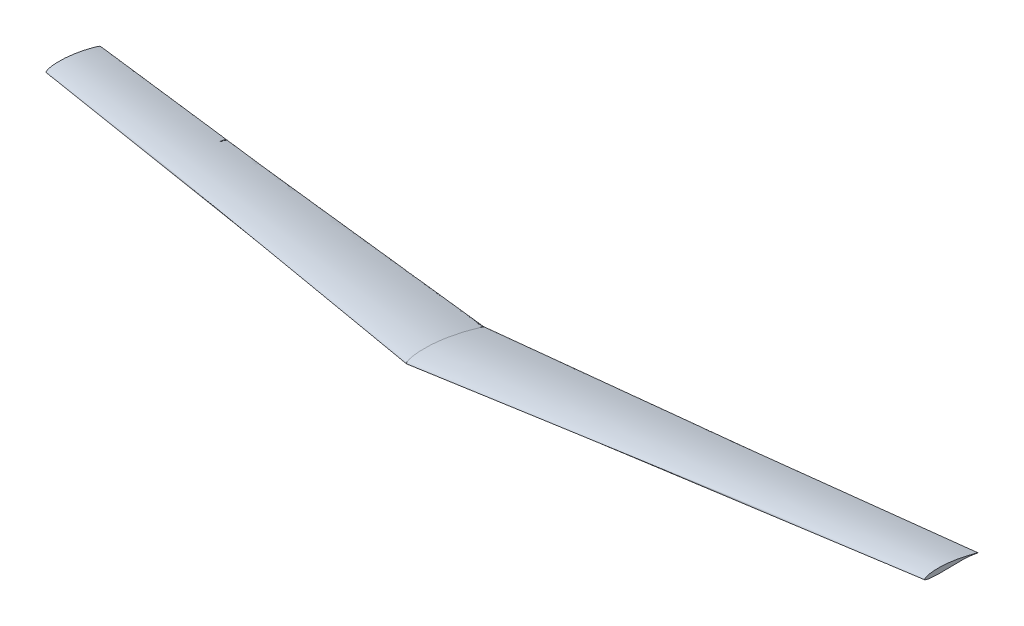
SolidWorks part; units mm, degrees
ref_plane "Front Plane" through (0, 0, 0) normal (0, 0, 1) x (1, 0, 0)
ref_plane "Top Plane" through (0, 0, 0) normal (0, 1, 0) x (1, 0, 0)
ref_plane "Right Plane" through (0, 0, 0) normal (1, 0, 0) x (0, 0, -1)
curve "Curve1" [suppressed]
  spline degree 3 poles (990.8864, 1.4626, 0) (1002.2961, -0.4112, 0) (990.8441, 1.8134, 0) (981.5017, 3.7617, 0) (958.72, 8.2838, 0) (930.7788, 13.882, 0) (894.3584, 21.0524, 0) (851.6093, 29.1958, 0) (802.7012, 37.9605, 0) (748.6568, 46.8178, 0) (690.3336, 55.2598, 0) (628.7485, 62.8578, 0) (564.9593, 69.3102, 0) (500.0529, 74.2901, 0) (435.1446, 77.6383, 0) (381.5431, 78.8952, 0) (339.5074, 78.8514, 0) (308.9256, 78.291, 0) (279.1596, 77.1918, 0) (250.3368, 75.5511, 0) (222.5834, 73.3929, 0) (196.0179, 70.7426, 0) (170.7576, 67.5923, 0) (146.9006, 64.0143, 0) (124.5538, 60.0239, 0) (103.8161, 55.6758, 0) (84.7697, 51.0327, 0) (67.4899, 46.1315, 0) (52.0474, 40.9763, 0) (38.4901, 35.5666, 0) (26.9107, 29.8179, 0) (17.3482, 23.8003, 0) (9.8808, 17.6898, 0) (4.4583, 11.8176, 0) (1.0945, 6.5163, 0) (-0.4235, 1.7367, 0) (0.8173, -2.5835, 0) (4.659, -5.507, 0) (10.1684, -7.8354, 0) (17.6608, -10.1699, 0) (27.1608, -12.5656, 0) (38.6719, -15.0199, 0) (52.1627, -17.3731, 0) (67.5741, -19.4941, 0) (84.8387, -21.2782, 0) (103.8748, -22.7648, 0) (124.6076, -23.8975, 0) (146.9475, -24.7252, 0) (170.7979, -25.1679, 0) (196.0544, -25.2499, 0) (222.6146, -24.8933, 0) (250.3648, -24.0804, 0) (279.1846, -22.7848, 0) (308.9466, -21.0099, 0) (339.5213, -18.768, 0) (381.5575, -15.3047, 0) (435.122, -10.2918, 0) (499.9862, -3.9917, 0) (564.857, 2.0129, 0) (628.629, 7.1599, 0) (690.2143, 10.984, 0) (748.5563, 13.2668, 0) (802.6371, 13.9274, 0) (851.5834, 13.0931, 0) (894.3694, 11.1362, 0) (930.8016, 8.4, 0) (958.7658, 5.6402, 0) (981.4948, 2.6953, 0) (990.8864, 1.4626, 0) (1002.2961, -0.4112, 0) (990.8441, 1.8134, 0) knots -0.01889 -0.00847 -0.00213 0 0.002148 0.00855 0.019093 0.033602 0.051812 0.073403 0.097969 0.12507 0.15422 0.18491 0.21662 0.248811 0.280949 0.312507 0.327907 0.342969 0.357635 0.371852 0.385562 0.398705 0.41124 0.423118 0.434295 0.444729 0.454376 0.463215 0.471223 0.478387 0.484735 0.490273 0.49502 0.498937 0.502002 0.504262 0.5061 0.508218 0.511109 0.514949 0.519768 0.525568 0.532309 0.53997 0.548516 0.557914 0.568141 0.57915 0.590897 0.603335 0.616414 0.630088 0.644296 0.658978 0.674077 0.689528 0.721211 0.753454 0.785684 0.817334 0.84785 0.876721 0.903468 0.927655 0.94889 0.966808 0.98111 0.99153 0.99787 1 1.002148 1.00855 1.019093 periodic
sketch "Sketch1" plane through (0, 0, 0) normal (1, 0, 0) x (0, 0, -1)
  line L0 (1494.292, -130.7336) -> (0, 0) construction
  line L1 (0, 0) -> (5.8072, 66.3764) construction
  line L2 (0, 0) -> (1494.292, 0) construction
  spline S3 degree 3 poles (1480.8596, -127.3779) (1497.6707, -131.6429) (1480.8414, -126.8482) (1467.1294, -122.7373) (1433.6627, -113.0547) (1392.6234, -101.1016) (1339.1137, -85.7106) (1276.2708, -68.053) (1204.3031, -48.6762) (1124.671, -28.5018) (1038.5911, -8.3988) (947.5278, 10.8615) (853.0235, 28.6927) (756.6606, 44.4666) (660.0853, 57.8023) (580.1395, 66.5612) (517.3119, 71.8914) (471.5356, 74.9795) (426.9096, 77.1576) (383.6234, 78.4053) (341.8692, 78.7424) (301.8269, 78.1915) (263.6712, 76.7259) (227.5579, 74.4409) (193.6485, 71.3458) (162.098, 67.5095) (133.0373, 63.0152) (106.5835, 57.9085) (82.8432, 52.1864) (61.8875, 45.8418) (43.8442, 38.7368) (28.7808, 30.9709) (16.8364, 22.7974) (7.9787, 14.7174) (2.271, 7.2265) (-0.6112, 0.2784) (0.6887, -6.3375) (6.0548, -11.1998) (13.9897, -15.3868) (24.8874, -19.8374) (38.7775, -24.6371) (55.6657, -29.7827) (75.5256, -35.0313) (98.2856, -40.1793) (123.8584, -45.0617) (152.117, -49.727) (182.9566, -54.0811) (216.2372, -58.1856) (251.8246, -61.9088) (289.5597, -65.2734) (329.2996, -68.1497) (370.8764, -70.497) (414.1136, -72.26) (458.8206, -73.4277) (504.802, -74.0019) (568.0694, -74.2218) (648.7647, -73.6057) (746.5125, -72.5163) (844.2323, -71.8695) (940.1997, -72.3633) (1032.7294, -74.5533) (1120.2142, -78.6306) (1201.1222, -84.5852) (1274.1651, -92.1149) (1337.8573, -100.5317) (1391.9537, -109.2974) (1433.3918, -117.0115) (1466.9821, -124.3302) (1480.8596, -127.3779) (1497.6707, -131.6429) (1480.8414, -126.8482) knots -0.01889 -0.00847 -0.00213 0 0.002148 0.00855 0.019093 0.033602 0.051812 0.073403 0.097969 0.12507 0.15422 0.18491 0.21662 0.248811 0.280949 0.312507 0.327907 0.342969 0.357635 0.371852 0.385562 0.398705 0.41124 0.423118 0.434295 0.444729 0.454376 0.463215 0.471223 0.478387 0.484735 0.490273 0.49502 0.498937 0.502002 0.504262 0.5061 0.508218 0.511109 0.514949 0.519768 0.525568 0.532309 0.53997 0.548516 0.557914 0.568141 0.57915 0.590897 0.603335 0.616414 0.630088 0.644296 0.658978 0.674077 0.689528 0.721211 0.753454 0.785684 0.817334 0.84785 0.876721 0.903468 0.927655 0.94889 0.966808 0.98111 0.99153 0.99787 1 1.002148 1.00855 1.019093 only from (1494.292, -130.7336) to (1494.292, -130.7336)
  dimension "D1" = 1500
  dimension "D2" = 5
ref_plane "Plane1" through (0, 0, 0) normal (0, 0.9962, -0.0872) x (1, -0.0003, -0.0038)
sketch "Sketch2" plane through (0, 0, 0) normal (0, 0.9962, -0.0872) x (1, -0.0003, -0.0038)
  line L0 (8500, 0) -> (0, 0) construction
  line L2 (8500, 0) -> (8500, 1498.7793) construction
  line L3 (5.7188, 1499.9891) -> (0, 0) construction
  line L4 (8500, 1498.7793) -> (8500, 2538.7793)
  line L5 (8500, 2538.7793) -> (5.7188, 1499.9891)
  line L6 (5.7188, 1499.9891) -> (0, 0)
  line L8 (0, 0) -> (8500, 1498.7793)
  point P0 (0, 0)
  point P9 (10000, 1763.2698)
  point P10 (0, 0)
  dimension "D1" = 8500
  dimension "D2" = 1498.7793
  dimension "D3" = 1040
ref_plane "Plane2" through (8494.2241, -133.4507, -1525.3485) normal (1, -0.0003, -0.0038) x (-0.0038, 0, -1)
sketch "Sketch6" plane through (8494.2241, -133.4507, -1525.3485) normal (1, -0.0003, -0.0038) x (-0.0038, 0, -1)
  line L2 (1037.3946, -73.5696) -> (0, 0) construction
  line L3 (0, 0) -> (6.3169, 89.0732) construction
  line L4 (0, 0) -> (1037.3946, 0) construction
  spline S3 degree 3 poles (1028.0443, -71.3966) (1039.7472, -74.1614) (1028.0257, -71.0296) (1018.4731, -68.3363) (995.1621, -62.006) (966.5756, -54.1882) (929.3048, -44.1295) (885.538, -32.606) (835.426, -19.9949) (779.9916, -6.9184) (720.0881, 6.0351) (656.7396, 18.3474) (591.0219, 29.6298) (524.0392, 39.4647) (456.9372, 47.6069) (401.4156, 52.7662) (357.8002, 55.7441) (326.031, 57.3622) (295.0696, 58.3627) (265.0477, 58.7334) (236.0982, 58.4904) (208.3456, 57.6513) (181.9113, 56.1997) (156.9022, 54.2034) (133.4302, 51.6705) (111.602, 48.6509) (91.5072, 45.2035) (73.2268, 41.3613) (56.8343, 37.1235) (42.3795, 32.4859) (29.9523, 27.3544) (19.5984, 21.7989) (11.4114, 15.9963) (5.3631, 10.2938) (1.4918, 5.0356) (-0.4269, 0.186) (0.5498, -4.3855) (4.3253, -7.695) (9.8739, -10.507) (17.4794, -13.4679) (27.1634, -16.6367) (38.9297, -20.011) (52.7573, -23.4228) (68.5942, -26.7318) (86.378, -29.8245) (106.0212, -32.736) (127.4501, -35.4023) (150.5684, -37.8678) (175.2815, -40.0426) (201.4794, -41.9442) (229.0615, -43.4845) (257.911, -44.637) (287.9048, -45.3656) (318.9108, -45.6647) (350.7935, -45.5378) (394.6554, -44.9679) (450.5896, -43.6195) (518.3397, -41.7483) (586.0755, -40.1843) (652.6096, -39.431) (716.7798, -39.8928) (777.4742, -41.7205) (833.6309, -44.9248) (884.353, -49.3107) (928.6031, -54.4184) (966.2049, -59.8775) (995.0195, -64.7521) (1018.3891, -69.4423) (1028.0443, -71.3966) (1039.7472, -74.1614) (1028.0257, -71.0296) knots -0.01889 -0.00847 -0.00213 0 0.002148 0.00855 0.019093 0.033602 0.051812 0.073403 0.097969 0.12507 0.15422 0.18491 0.21662 0.248811 0.280949 0.312507 0.327907 0.342969 0.357635 0.371852 0.385562 0.398705 0.41124 0.423118 0.434295 0.444729 0.454376 0.463215 0.471223 0.478387 0.484735 0.490273 0.49502 0.498937 0.502002 0.504262 0.5061 0.508218 0.511109 0.514949 0.519768 0.525568 0.532309 0.53997 0.548516 0.557914 0.568141 0.57915 0.590897 0.603335 0.616414 0.630088 0.644296 0.658978 0.674077 0.689528 0.721211 0.753454 0.785684 0.817334 0.84785 0.876721 0.903468 0.927655 0.94889 0.966808 0.98111 0.99153 0.99787 1 1.002148 1.00855 1.019093 only from (1037.3946, -73.5696) to (1037.3946, -73.5696)
  point P2 (0, 0)
  point P6 (0, 0)
  point P7 (43.8629, 60.7818)
  point P8 (0, 0)
  point P9 (597.7267, 52.1805)
  point P10 (598.4969, -42.444)
  point P28 (0, 0)
  dimension "D1" = 1040
  dimension "D2" = 4.056
loft "Loft3" add profiles "Sketch1", "Sketch6" connector at (0, 75.2472, -464.3315) connector at (8492.8329, -78.6379, -1896.4237)
mirror "Mirror2" about plane through (0, 0, 0) normal (1, 0, 0) of "Loft3"
equation "\"span\"= 17"
equation "\"D1@Sketch2\"=\"span\"/2"
equation "\"cr\" = 2.6"
equation "\"tr\"= 0.4"
equation "\"AR\" = \"span\" ^ 2 / \"S\""
equation "\"ct\"= \"tr\" * \"cr\""
equation "\"S\" = 0.5 * ( \"cr\" + \"ct\" ) * \"span\""
equation "\"theta\"= 10deg"
equation "\"l\"= tan ( \"theta\" ) * \"span\" / 2"
equation "\"D2@Sketch2\"=\"l\""
equation "\"D3@Sketch2\"=\"ct\""
equation "\"D1@Sketch6\"=\"ct\""
